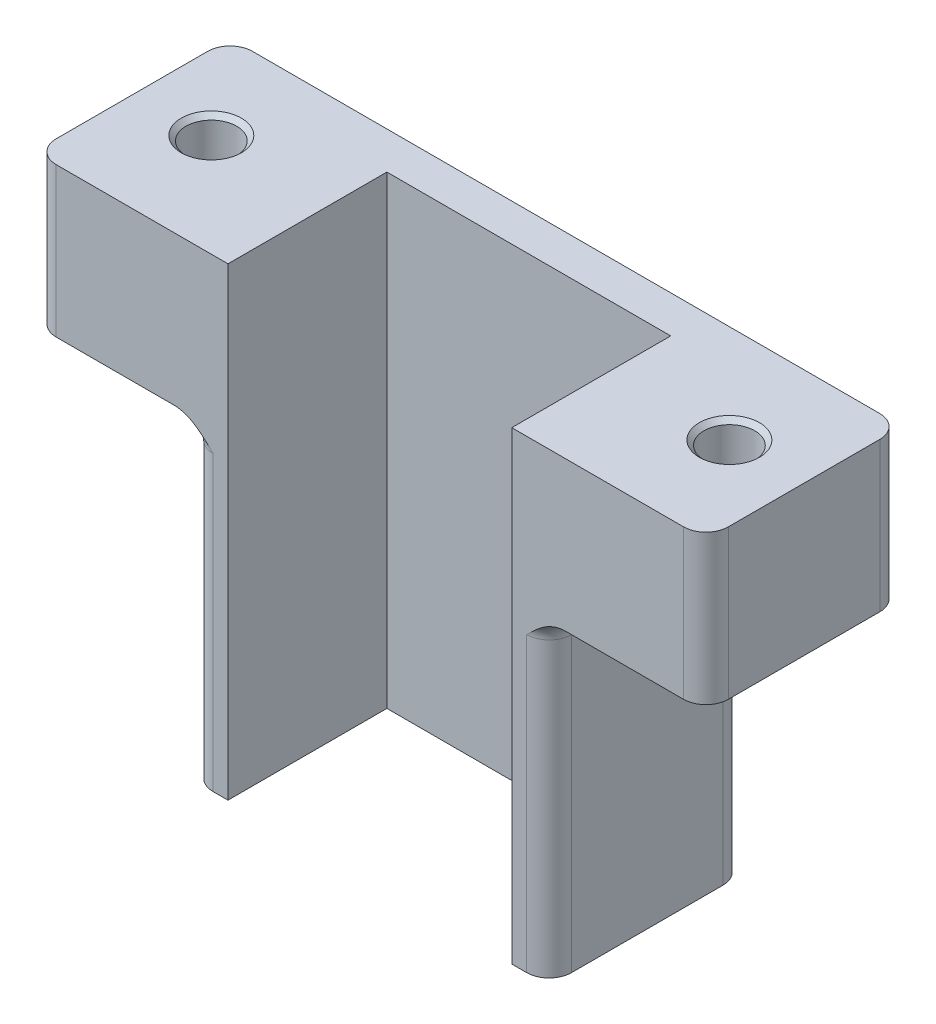
SolidWorks part; units mm, degrees
material "K110"
ref_plane "Front Plane" through (0, 0, 0) normal (0, 0, 1) x (1, 0, 0)
ref_plane "Top Plane" through (0, 0, 0) normal (0, 1, 0) x (1, 0, 0)
ref_plane "Right Plane" through (0, 0, 0) normal (1, 0, 0) x (0, 0, -1)
sketch "Sketch1" plane through (0, 0, 0) normal (0, 1, 0) x (1, 0, 0)
  line L0 (549.56, 7.51) -> (549.56, -13.77) construction
  line L1 (504.56, -13.77) -> (594.56, -13.77)
  line L2 (504.56, -13.77) -> (504.56, 12.51)
  line L3 (504.56, 12.51) -> (594.56, 12.51)
  line L4 (594.56, -13.77) -> (594.56, 12.51)
  line L5 (504.56, -13.77) -> (594.56, 12.51) construction
  line L6 (504.56, 12.51) -> (594.56, -13.77) construction
  line L7 (549.56, 7.51) -> (549.56, -129.77) construction
  line L8 (504.56, -0.63) -> (594.56, -0.63) construction
  line L9 (504.56, 9.51) -> (504.56, -10.77) construction
  line L10 (594.56, -10.77) -> (594.56, 9.51) construction
  line L11 (591.56, 12.51) -> (507.56, 12.51) construction
  point P0 (0, 0)
  dimension "D1" = 90
extrude "Boss-Extrude1" add sketch "Sketch1" against normal blind 62.2
fillet "Fillet1" radius 3 4 edges at (594.56, -31.1, -12.51) (594.56, -31.1, 13.77) (504.56, -31.1, -12.51) (504.56, -31.1, 13.77)
sketch "Sketch4" plane through (0, -62.2, 0) normal (0, -1, 0) x (1, 0, 0)
  line L0 (573.56, 13.77) -> (568.56, 13.77) construction
  line L1 (568.56, 13.77) -> (568.56, -7.51) construction
  line L2 (568.56, -7.51) -> (530.56, -7.51) construction
  line L3 (530.56, -7.51) -> (530.56, 13.77) construction
  line L4 (530.56, 13.77) -> (525.56, 13.77) construction
  line L5 (525.56, 13.77) -> (525.56, -12.51) construction
  line L6 (525.56, -12.51) -> (573.56, -12.51) construction
  line L7 (573.56, 13.77) -> (573.56, -12.51) construction
  line L8 (570.56, 13.77) -> (568.56, 13.77)
  line L9 (568.56, 13.77) -> (568.56, -7.51)
  line L10 (568.56, -7.51) -> (530.56, -7.51)
  line L11 (530.56, -7.51) -> (530.56, 13.77)
  line L12 (530.56, 13.77) -> (528.56, 13.77)
  line L13 (525.56, 10.77) -> (525.56, -9.51)
  line L14 (528.56, -12.51) -> (570.56, -12.51)
  line L15 (573.56, 10.77) -> (573.56, -9.51)
  arc A0 (570.56, -12.51) -> (573.56, -9.51) centre (570.56, -9.51) ccw
  arc A1 (570.56, 13.77) -> (573.56, 10.77) centre (570.56, 10.77) cw
  arc A2 (528.56, 13.77) -> (525.56, 10.77) centre (528.56, 10.77) ccw
  arc A3 (525.56, -9.51) -> (528.56, -12.51) centre (528.56, -9.51) ccw
  dimension "D1" = 3
sketch "Sketch5" plane through (0, 0, 0) normal (0, 1, 0) x (1, 0, 0)
  line L3 (530.56, -13.77) -> (568.56, -13.77)
  line L4 (530.56, 7.51) -> (530.56, -13.77) construction
  line L5 (568.56, 7.51) -> (530.56, 7.51) construction
  line L6 (568.56, -13.77) -> (568.56, 7.51) construction
  line L7 (530.56, 7.51) -> (530.56, -13.77)
  line L8 (568.56, 7.51) -> (530.56, 7.51)
  line L9 (568.56, -13.77) -> (568.56, 7.51)
extrude "Cut-Extrude2" cut sketch "Sketch5" against normal through all
sketch "Sketch11" plane through (0, -62.2, 0) normal (0, -1, 0) x (1, 0, 0)
  line L18 (594.56, 10.77) -> (594.56, -9.51) construction
  line L19 (504.56, -9.51) -> (504.56, 10.77) construction
  line L20 (594.56, 10.77) -> (594.56, -9.51)
  line L21 (504.56, -9.51) -> (504.56, 10.77)
  line L22 (573.56, 10.77) -> (573.56, -9.51) construction
  line L23 (525.56, -9.51) -> (525.56, 10.77) construction
  line L24 (573.56, 10.77) -> (573.56, -9.51)
  line L25 (525.56, -9.51) -> (525.56, 10.77)
  line L26 (507.56, 13.77) -> (528.56, 13.77)
  line L27 (528.56, -12.51) -> (507.56, -12.51)
  line L28 (591.56, -12.51) -> (570.56, -12.51)
  line L29 (591.56, 13.77) -> (570.56, 13.77)
  arc A8 (594.56, 10.77) -> (591.56, 13.77) centre (591.56, 10.77) ccw construction
  arc A9 (591.56, -12.51) -> (594.56, -9.51) centre (591.56, -9.51) ccw construction
  arc A10 (504.56, -9.51) -> (507.56, -12.51) centre (507.56, -9.51) ccw construction
  arc A11 (507.56, 13.77) -> (504.56, 10.77) centre (507.56, 10.77) ccw construction
  arc A12 (594.56, 10.77) -> (591.56, 13.77) centre (591.56, 10.77) ccw
  arc A13 (591.56, -12.51) -> (594.56, -9.51) centre (591.56, -9.51) ccw
  arc A14 (504.56, -9.51) -> (507.56, -12.51) centre (507.56, -9.51) ccw
  arc A15 (507.56, 13.77) -> (504.56, 10.77) centre (507.56, 10.77) ccw
  arc A16 (573.56, 10.77) -> (570.56, 13.77) centre (570.56, 10.77) ccw construction
  arc A17 (570.56, -12.51) -> (573.56, -9.51) centre (570.56, -9.51) ccw construction
  arc A18 (525.56, -9.51) -> (528.56, -12.51) centre (528.56, -9.51) ccw construction
  arc A19 (528.56, 13.77) -> (525.56, 10.77) centre (528.56, 10.77) ccw construction
  arc A20 (573.56, 10.77) -> (570.56, 13.77) centre (570.56, 10.77) ccw
  arc A21 (570.56, -12.51) -> (573.56, -9.51) centre (570.56, -9.51) ccw
  arc A22 (525.56, -9.51) -> (528.56, -12.51) centre (528.56, -9.51) ccw
  arc A23 (528.56, 13.77) -> (525.56, 10.77) centre (528.56, 10.77) ccw
extrude "Cut-Extrude3" cut sketch "Sketch11" against normal up to surface (42.2 mm away) up to face at (549.56, -62.2, 1.4633)
hole_wizard "M8 Tapped Hole1" positions "Sketch12" profile "Sketch8" tap size "M8" standard "ISO"
sketch "Sketch12" plane through (0, 0, 0) normal (0, 1, 0) x (1, 0, 0)
  line L4 (504.56, 0) -> (530.56, 0) construction
  line L8 (594.56, -0.63) -> (568.56, -0.63) construction
  line L9 (594.56, -10.77) -> (594.56, 9.51) construction
  line L10 (568.56, -13.77) -> (568.56, 7.51) construction
  line L12 (594.56, -10.77) -> (594.56, 9.51) construction
  line L13 (530.56, 7.51) -> (530.56, -13.77) construction
  line L14 (504.56, 9.51) -> (504.56, -10.77) construction
  point P0 (514.56, 0)
  point P2 (584.56, -0.63)
  point P33 (0, 0)
  point P36 (0, 0)
  point P39 (0, 0)
  point P40 (0, 0)
  point P41 (513.8698, 1.1788)
  dimension "D1" = 10
  dimension "D2" = 10
sketch "Sketch8" plane through (514.56, 0, 0) normal (1, 0, 0) x (0, 0, 1)
  line L0 (0, 0) -> (0, 19.75)
  line L1 (0, 19.75) -> (3.4, 17.7071)
  line L2 (3.4, 17.7071) -> (3.4, 0.625)
  line L3 (3.4, 0.625) -> (4.025, 0)
  line L5 (4.025, 0) -> (0, 0)
  line L6 (-3.4, 0.625) -> (-4.025, 0) construction
  line L10 (0, 19.75) -> (-3.4, 17.7071) construction
  line L11 (0, -6.35) -> (0, 107.95) construction
  dimension "Tap Drill Dia." = 6.8
  dimension "Tap Drill Depth" = 19.75
  dimension "Near C'Sink Dia." = 8.05
  dimension "Near C'Sink Angle" = 90
  dimension "Drill Angle" = 118
cosmetic thread "Hole Thread3" parameters "D1"=16, "D2"=8
cosmetic thread "Hole Thread4" parameters "D1"=16, "D2"=8
fillet "Fillet2" radius 3 6 edges at (572.6813, -20, -11.6313) (572.6813, -20, 12.8913) (526.4387, -20, 12.8913) (526.4387, -20, -11.6313) (573.56, -20, 0.63) (525.56, -20, 0.63)
